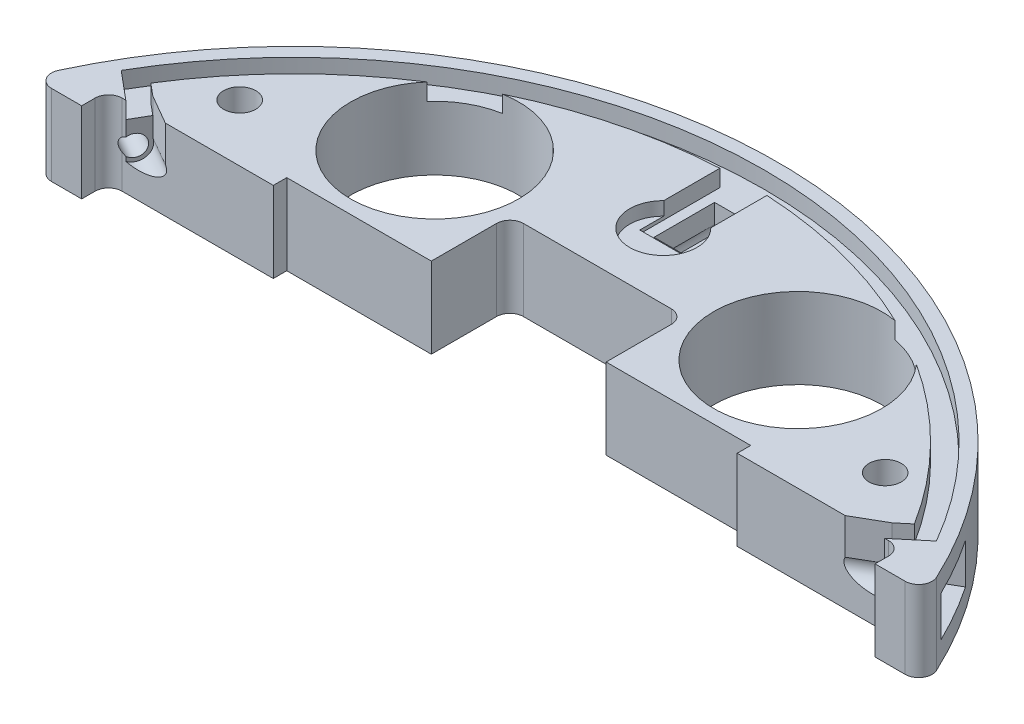
SolidWorks part; units mm, degrees
material "ABS"
ref_plane "Front Plane" through (0, 0, 0) normal (0, 0, 1) x (1, 0, 0)
ref_plane "Top Plane" through (0, 0, 0) normal (0, 1, 0) x (1, 0, 0)
ref_plane "Right Plane" through (0, 0, 0) normal (1, 0, 0) x (0, 0, -1)
sketch "Sketch1" plane through (0, 0, 0) normal (0, 1, 0) x (1, 0, 0)
  line L0 (0, -85) -> (-32.2211, -64.3879) construction
  line L1 (0, -85) -> (0, 0) construction
  arc A0 (36.2245, -62.2237) -> (-36.2245, -62.2237) centre (0, 0) ccw
  arc A1 (29.8119, -61.0352) -> (-29.8119, -61.0352) centre (0, -85) ccw
  arc A2 (36.2245, -62.2237) -> (29.8119, -61.0352) centre (33.7089, -57.9026) cw
  arc A3 (-29.8119, -61.0352) -> (-36.2245, -62.2237) centre (-33.7089, -57.9026) cw
  dimension "D1" = 144
  dimension "D2" = 76.5
  dimension "D4" = 5
  dimension "D3" = 85
extrude "Boss-Extrude1" add sketch "Sketch1" along normal mid plane 12
sketch "solenoid placement" plane through (0, 6, 0) normal (0, 1, 0) x (1, 0, 0)
  line L0 (0, 0) -> (0, -36) construction
  line L5 (-19, -36) -> (19, -36)
  line L7 (19, -36) -> (19, 28)
  line L9 (19, 28) -> (-19, 28)
  line L11 (-19, 28) -> (-19, -36)
  circle A1 centre (0, 0) radius 72 construction
  arc A2 (36.2245, -62.2237) -> (-36.2245, -62.2237) centre (0, 0) ccw construction
  dimension "D1" = 36
  dimension "D2" = 64
  dimension "D3" = 38
extrude "Cut-Extrude1" cut sketch "solenoid placement" against normal through all
sketch "Sketch4" plane through (0, 6, 0) normal (0, 1, 0) x (1, 0, 0)
  line L1 (-13, 28) -> (13, 28)
  line L2 (-13, 28) -> (-13, 43.2)
  line L4 (13, 28) -> (13, 43.2)
  line L5 (11, 45.2) -> (-11, 45.2)
  line L6 (19, 28) -> (-19, 28) construction
  arc A0 (11, 45.2) -> (13, 43.2) centre (11, 43.2) cw
  arc A1 (-11, 45.2) -> (-13, 43.2) centre (-11, 43.2) ccw
  point P6 (0, 28)
  dimension "D1" = 2
  dimension "D2" = 26
  dimension "D3" = 17.2
extrude "Cut-Extrude4" cut sketch "Sketch4" against normal through all
sketch "Sketch5" plane through (0, 6, 0) normal (0, 1, 0) x (1, 0, 0)
  line L0 (0, 0) -> (0, 72) construction
  arc A0 (36.2245, -62.2237) -> (-36.2245, -62.2237) centre (0, 0) ccw construction
  circle A1 centre (27, 48) radius 12.5
  circle A3 centre (-27, 48) radius 12.5
  dimension "D3" = 25
  dimension "D1" = 27
  dimension "D2" = 48
extrude "Cut-Extrude5" cut sketch "Sketch5" against normal through all
sketch "Sketch6" plane through (0, 6, 0) normal (0, 1, 0) x (1, 0, 0)
  line L0 (0, 0) -> (0, 72) construction
  arc A0 (36.2245, -62.2237) -> (-36.2245, -62.2237) centre (0, 0) ccw construction
  circle A1 centre (48, 40) radius 2.4
  circle A6 centre (-48, 40) radius 2.4
  dimension "D3" = 4.8
  dimension "D1" = 48
  dimension "D2" = 40
extrude "Cut-Extrude6" cut sketch "Sketch6" against normal through all
sketch "Sketch3" plane through (0, 6, 0) normal (0, 1, 0) x (1, 0, 0)
  line L1 (-72, -31.5) -> (72, -31.5) construction
  line L2 (-72, -31.5) -> (-72, 27.5)
  line L3 (-59, 31.5) -> (0, 31.5)
  line L4 (72, -31.5) -> (72, 27.5)
  line L5 (0, -31.5) -> (0, 31.5) construction
  line L6 (72, 27.5) -> (59, 27.5)
  line L9 (0, 31.5) -> (59, 31.5)
  line L10 (-72, -31.5) -> (-72, -101.6464)
  line L11 (72, -31.5) -> (72, -101.6464)
  line L12 (72, -101.6464) -> (-72, -101.6464)
  line L13 (59, 27.5) -> (59, 31.5)
  line L14 (-59, 27.5) -> (-59, 31.5)
  line L15 (-72, 27.5) -> (-59, 27.5)
  arc A0 (36.2245, -62.2237) -> (-36.2245, -62.2237) centre (0, 0) ccw construction
  point P0 (0, 0)
  dimension "D2" = 13
  dimension "D1" = 63
  dimension "D3" = 4
extrude "Cut-Extrude3" cut sketch "Sketch3" against normal through all
sketch "Sketch7" plane through (0, 0, 0) normal (0, 1, 0) x (1, 0, 0)
  line L0 (0, 0) -> (62.3538, 36) construction
  line L1 (0, 0) -> (-62.3538, 36) construction
  line L2 (0, 0) -> (0, 72) construction
  arc A0 (0, 72) -> (62.3538, 36) centre (0, 0) cw construction
  arc A1 (0, 72) -> (-62.3538, 36) centre (0, 0) ccw construction
  arc A2 (66.5413, 27.5) -> (-66.5413, 27.5) centre (0, 0) ccw construction
  dimension "D1" = 120
fillet "Fillet1" radius 2 4 edges at (-66.5413, 0, -27.5) (-59, 0, -31.5) (59, 0, -31.5) (66.5413, 0, -27.5)
sketch "Sketch8" plane through (0, 0, 0) normal (0, 1, 0) x (1, 0, 0)
  line L0 (5, 71.8262) -> (5, 68.8262)
  line L1 (0, 0) -> (64.7033, 31.583) construction
  line L2 (64.7033, 31.583) -> (59.7033, 40.2432) construction
  line L3 (64.7033, 31.583) -> (62.1052, 30.083)
  line L4 (62.1052, 30.083) -> (57.1052, 38.7432)
  line L5 (59.7033, 40.2432) -> (57.1052, 38.7432)
  line L6 (0, 0) -> (59.7033, 40.2432) construction
  line L7 (5, 68.8262) -> (-5, 68.8262)
  line L8 (-5, 71.8262) -> (-5, 68.8262)
  line L9 (5, 71.8262) -> (-5, 71.8262) construction
  line L10 (-59.7033, 40.2432) -> (-57.1052, 38.7432)
  line L11 (-57.1052, 38.7432) -> (-62.1052, 30.083)
  line L12 (-64.7033, 31.583) -> (-62.1052, 30.083)
  line L13 (-59.7033, 40.2432) -> (-64.7033, 31.583) construction
  arc A0 (59.7033, 40.2432) -> (64.7033, 31.583) centre (0, 0) cw
  arc A2 (-5, 71.8262) -> (5, 71.8262) centre (0, 0) cw
  arc A3 (-64.7033, 31.583) -> (-59.7033, 40.2432) centre (0, 0) cw
  point P4 (62.3538, 36)
  point P10 (-62.3538, 36)
  point P18 (0, 0)
  dimension "D1" = 10
  dimension "D2" = 3
extrude "Cut-Extrude7" cut sketch "Sketch8" against normal mid plane 6
sketch "Sketch10" plane through (0, 6, 0) normal (0, 1, 0) x (1, 0, 0)
  line L0 (0, 0) -> (0, 55) construction
  circle A0 centre (0, 55) radius 5
  dimension "D2" = 10
  dimension "D1" = 55
extrude "Cut-Extrude9" cut sketch "Sketch10" against normal blind 2
sketch "Sketch11" plane through (0, 6, 0) normal (0, 1, 0) x (1, 0, 0)
  line L1 (34.5, -33.5) -> (-34.5, -33.5)
  line L2 (34.5, -33.5) -> (34.5, 33.5)
  line L3 (34.5, 33.5) -> (-34.5, 33.5)
  line L4 (-34.5, -33.5) -> (-34.5, 33.5)
  line L5 (34.5, -33.5) -> (-34.5, 33.5) construction
  line L6 (34.5, 33.5) -> (-34.5, -33.5) construction
  point P0 (0, 0)
  dimension "D1" = 67
  dimension "D2" = 69
extrude "Cut-Extrude10" cut sketch "Sketch11" against normal through all
sketch "Sketch13" plane through (-59.6052, 0, -34.4131) normal (-0.866, 0, -0.5) x (-0.5, 0, 0.866)
  circle A0 centre (0, 0) radius 1.55
  dimension "D1" = 3.1
extrude "Cut-Extrude11" cut sketch "Sketch13" against normal blind 4.2
sketch "Sketch14" plane through (-55.9679, 0, -32.3131) normal (-0.866, 0, -0.5) x (-0.5, 0, 0.866)
  circle A0 centre (0, 0) radius 2.1
  dimension "D1" = 4.2
extrude "Cut-Extrude12" cut sketch "Sketch14" against normal blind 9
sketch "Sketch15" plane through (-55.9679, 0, -32.3131) normal (0.866, 0, 0.5) x (0.5, 0, -0.866)
  line L1 (-2, 0) -> (2, 0)
  line L2 (-2, 0) -> (-2, 10.8827)
  line L3 (-2, 10.8827) -> (2, 10.8827)
  line L4 (2, 0) -> (2, 10.8827)
  point P0 (0, 0)
  dimension "D1" = 4
extrude "Cut-Extrude13" cut sketch "Sketch15" along normal blind 9
pattern_circular "CirPattern1" count 3 over 120 about axis through (0, 6, 0) along (0, -1, 0) of "Cut-Extrude11", "Cut-Extrude12", "Cut-Extrude13"
sketch "Sketch16" plane through (0, 6, 0) normal (0, 1, 0) x (1, 0, 0)
  line L0 (0, 0) -> (-62.3538, 36) construction
  line L1 (0, 0) -> (62.3538, 36) construction
  line L4 (-56.4374, 31.5) -> (-60.6218, 35)
  line L5 (3.5, 55) -> (-3.5, 55)
  line L6 (3.5, 55) -> (3.5, 66.9085)
  line L7 (-54.9679, 34.0451) -> (-56.7827, 35.5631)
  line L8 (-3.5, 55) -> (-3.5, 66.9085)
  line L9 (56.4374, 31.5) -> (60.6218, 35)
  line L10 (54.9679, 34.0451) -> (56.7827, 35.5631)
  line L11 (54.9679, 34.0451) -> (50.5596, 31.5) construction
  line L12 (54.9679, 34.0451) -> (56.4374, 31.5) construction
  line L13 (-54.9679, 34.0451) -> (-56.4374, 31.5)
  line L14 (54.9679, 34.0451) -> (56.4374, 31.5)
  arc A0 (60.6218, 35) -> (-60.6218, 35) centre (0, 0) ccw
  arc A1 (56.7827, 35.5631) -> (3.5, 66.9085) centre (0, 0) ccw
  arc A2 (-2, 59.5826) -> (2, 59.5826) centre (0, 55) ccw construction
  arc A3 (-3.5, 66.9085) -> (-56.7827, 35.5631) centre (0, 0) ccw
  point P15 (0, 55)
  dimension "D1" = 3
  dimension "D2" = 140
  dimension "D3" = 7
extrude "Cut-Extrude14" cut sketch "Sketch16" against normal blind 2.5
equation "\"smallPulleyTeeth\"= 30"
equation "\"largePulleyTeeth\"= 30"
equation "\"eighthThick\"= 3.0mm"
equation "\"sixteenthThick\" = 1.7mm"
equation "\"quarterThick\"=6.0mm"
equation "\"OD\" = 145mm"
equation "\"puckAngle\" = 60.5deg"
equation "\"puckDiam\" = 76.5mm"
equation "\"D2@Sketch1\"=\"puckDiam\""
equation "\"D1@Boss-Extrude1\"=\"eighthThick\"*4"
equation "\"axlePress\" = 5.9mm"
equation "\"press\" = 0.2mm"
equation "\"wheelClear\" = 0.3mm"
equation "\"10-32clear\" = 4.8mm"
equation "\"6-32clear\" = 3.3mm"
equation "\"8-32clear\" = 4.0mm"
equation "\"wheelHeight\" = 22mm"
equation "\"wheelWell\" = 65mm"
equation "\"puckDist\" = 85mm"
equation "\"scoopFillet\" = 5mm"
equation "\"4-40clear\" = 3.0mm"
equation "\"D3@Sketch1\"=\"puckDist\""
equation "\"D4@Sketch1\"=\"scoopFillet\""
equation "\"D3@Sketch6\"=\"10-32clear\""
equation "\"D2@Sketch8\"=\"eighthThick\""
equation "\"10-32tap\" = 4.45mm"
equation "\"ledSmall\" = 3.1mm"
equation "\"ledLarge\" = 4.2mm"
equation "\"ledLength\" = 4.2mm"
equation "\"D1@Sketch13\"=\"ledSmall\""
equation "\"D1@Cut-Extrude11\"=\"ledLength\""
equation "\"D1@Sketch14\"=\"ledLarge\""
